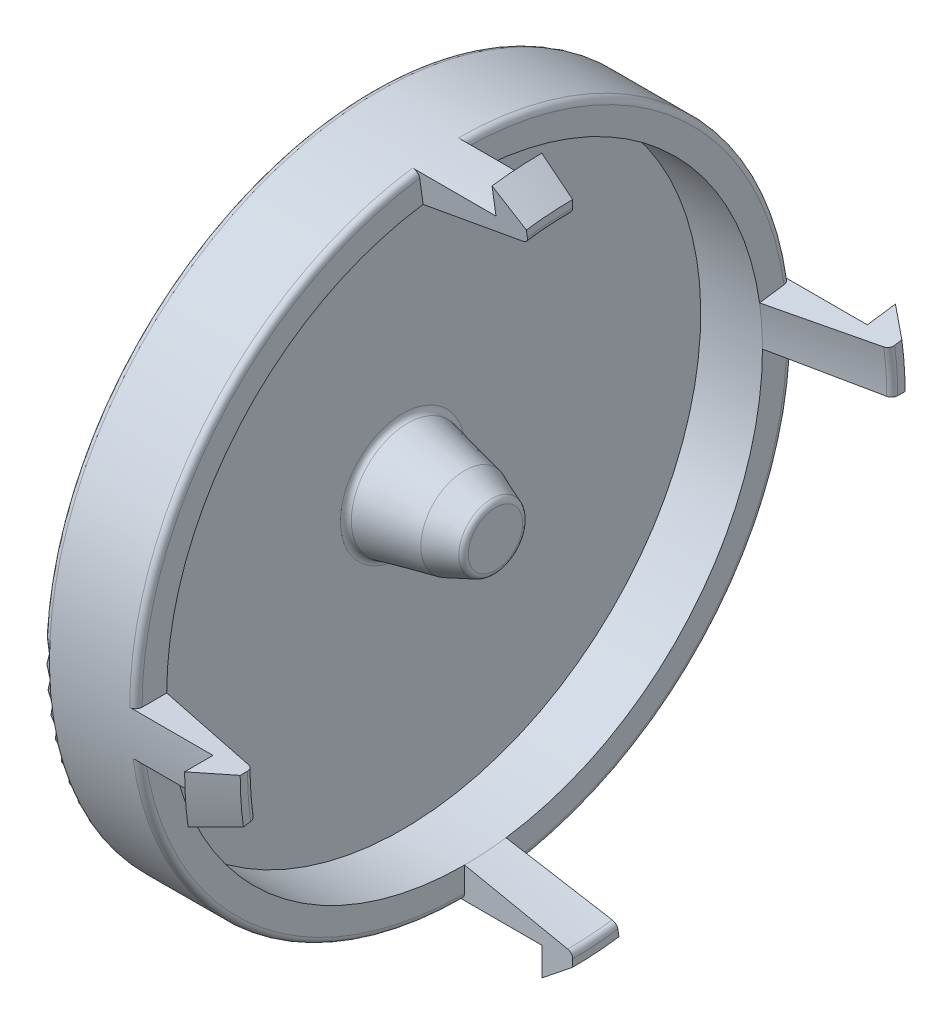
SolidWorks part; units mm, degrees
material "AISI 321 Annealed Stainless Steel (SS)"
ref_plane "Front Plane" through (0, 0, 0) normal (0, 0, 1) x (1, 0, 0)
ref_plane "Top Plane" through (0, 0, 0) normal (0, 1, 0) x (1, 0, 0)
ref_plane "Right Plane" through (0, 0, 0) normal (1, 0, 0) x (0, 0, -1)
sketch "Sketch1" plane through (0, 0, 0) normal (0, 0, 1) x (1, 0, 0)
  line L0 (0, 5.325) -> (1, 5.325)
  line L1 (0, 5.325) -> (-0.5, 5.325)
  line L4 (1, 0) -> (1.5, 0)
  line L6 (-0.5, 4.885) -> (-0.5, 1.49)
  line L7 (1, 0) -> (0.25, 0)
  line L8 (1, 5.325) -> (1, 4.825)
  line L10 (1, 0) -> (-0.5, 0)
  line L11 (1, 0.71) -> (0, 0.93)
  line L12 (-0.5, 5.325) -> (-0.5, 0)
  line L13 (1.5, 0) -> (1.5, 0.5077)
  line L14 (1, 4.825) -> (0, 4.825)
  line L15 (1, 0.71) -> (1.5, 0.5077)
  line L16 (0, 4.825) -> (0, 0.93)
  dimension "D1" = 1
  dimension "D2" = 4.825
  dimension "D3" = 0.5
  dimension "D4" = 0.5
  dimension "D5" = 0.75
revolve "Revolve2" add sketch "Sketch1" angle 360 about L10
sketch "Sketch4" plane through (0, 0, 0) normal (0, 0, 1) x (1, 0, 0)
  line L1 (2.75, 5.185) -> (2.75, 5.385)
  line L2 (2.75, 5.385) -> (2.25, 5.785)
  line L3 (2.25, 5.785) -> (2.25, 5.325)
  line L4 (2.25, 5.325) -> (1, 5.325)
  line L5 (1, 5.325) -> (1, 5.185)
  line L6 (0, 0) -> (3.1924, 0) construction
  line L7 (1, 5.185) -> (1, 4.825)
  line L8 (1, 4.825) -> (2.75, 5.185)
revolve "Revolve6" add sketch "Sketch4" angle 8 about L6
pattern_circular "CirPattern2" count 4 over 360 of "Revolve6"
fillet "Fillet2" radius 0.1 11 edges at (2.75, -0.3617, 5.1724) (2.75, -5.1724, -0.3617) (2.75, 0.3617, -5.1724) (2.75, 5.1724, 0.3617) (0, 0.93, 0) (1.5, 0.5077, 0) (-0.5, 5.325, 0)
